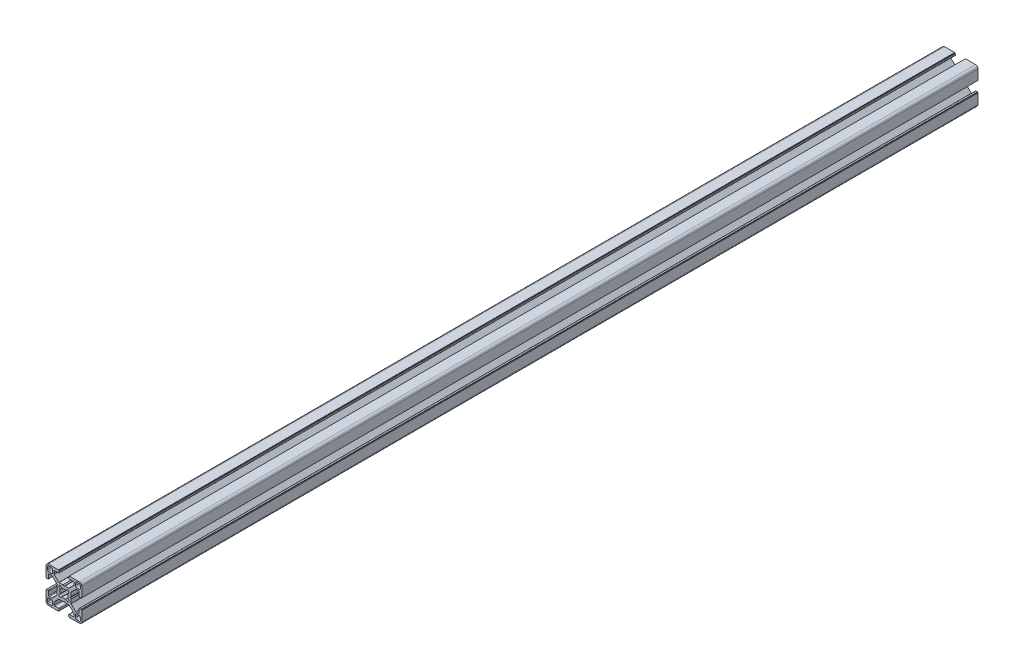
SolidWorks part; units mm, degrees
ref_plane "Front Plane" through (0, 0, 0) normal (0, 0, 1) x (1, 0, 0)
ref_plane "Top Plane" through (0, 0, 0) normal (0, 1, 0) x (1, 0, 0)
ref_plane "Right Plane" through (0, 0, 0) normal (1, 0, 0) x (0, 0, -1)
sketch "Sketch1" plane through (0, 0, 0) normal (0, 0, 1) x (1, 0, 0)
  line L0 (-15, 0) -> (15, 0) construction
  line L1 (0, -15) -> (0, 15) construction
  line L2 (-4.5, 15) -> (4.5, 15) construction
  line L3 (-4, -15) -> (4, -15) construction
  line L4 (-4.5, 15) -> (-4.5, 14.5)
  line L5 (-4.5, 14.5) -> (-4, 14.5)
  line L6 (-4, 14.5) -> (-4, 13.29)
  line L7 (-4.5, 12.79) -> (-7.7675, 12.79)
  line L8 (-8.2675, 12.29) -> (-8.2675, 10.2707)
  line L9 (-8.1211, 9.9171) -> (-4.3504, 6.1464)
  line L10 (-3.9968, 6) -> (0, 6)
  line L11 (0, 0) -> (-15, 15) construction
  line L12 (-4.5, 15) -> (-12.968, 15)
  line L14 (-12.705, 9.5135) -> (-10.5135, 9.5135)
  line L15 (-13.705, 10.5135) -> (-13.705, 12.705)
  line L16 (-12.705, 13.705) -> (-10.5135, 13.705)
  line L17 (-9.5135, 10.5135) -> (-9.5135, 12.705)
  line L18 (-13.705, 9.5135) -> (-9.5135, 13.705) construction
  line L19 (-13.705, 13.705) -> (-9.5135, 9.5135) construction
  line L20 (-3.1568, 4.5038) -> (-1.5303, 3.1477) construction
  line L21 (-4.5038, 3.1568) -> (-3.1477, 1.5303) construction
  line L22 (-6, 3.9968) -> (-6, 0)
  line L23 (-9.9171, 8.1211) -> (-6.1464, 4.3504)
  line L24 (-15, 4.5) -> (-15, 12.968)
  line L25 (-12.29, 8.2675) -> (-10.2707, 8.2675)
  line L26 (-12.79, 4.5) -> (-12.79, 7.7675)
  line L27 (-14.5, 4) -> (-13.29, 4)
  line L28 (-14.5, 4.5) -> (-14.5, 4)
  line L29 (-15, 4.5) -> (-14.5, 4.5)
  circle A0 centre (0, 0) radius 3.5
  arc A1 (-12.968, 15) -> (-15, 12.968) centre (-12.968, 12.968) ccw
  circle A2 centre (0, 0) radius 5.5 construction
  arc A3 (-10.5135, 9.5135) -> (-9.5135, 10.5135) centre (-10.5135, 10.5135) ccw
  arc A4 (-13.705, 12.705) -> (-12.705, 13.705) centre (-12.705, 12.705) cw
  arc A5 (-10.5135, 13.705) -> (-9.5135, 12.705) centre (-10.5135, 12.705) cw
  arc A6 (-12.705, 9.5135) -> (-13.705, 10.5135) centre (-12.705, 10.5135) cw
  arc A7 (-12.79, 4.5) -> (-13.29, 4) centre (-13.29, 4.5) cw
  arc A8 (-12.29, 8.2675) -> (-12.79, 7.7675) centre (-12.29, 7.7675) ccw
  arc A9 (-9.9171, 8.1211) -> (-10.2707, 8.2675) centre (-10.2707, 7.7675) ccw
  arc A10 (-6, 3.9968) -> (-6.1464, 4.3504) centre (-6.5, 3.9968) ccw
  arc A11 (-4.3504, 6.1464) -> (-3.9968, 6) centre (-3.9968, 6.5) ccw
  arc A12 (-4, 13.29) -> (-4.5, 12.79) centre (-4.5, 13.29) cw
  arc A13 (-7.7675, 12.79) -> (-8.2675, 12.29) centre (-7.7675, 12.29) ccw
  arc A14 (-8.2675, 10.2707) -> (-8.1211, 9.9171) centre (-7.7675, 10.2707) ccw
  point P4 (0, 0)
  point P8 (0, 0)
  point P13 (0, 15)
  point P15 (0, -15)
  point P16 (0, 6)
  point P23 (-11.6092, 11.6093)
  point P26 (0, 6)
  point P62 (-12.79, 4)
  point P65 (-12.79, 8.2675)
  point P68 (-10.0636, 8.2675)
  point P71 (-6, 4.2039)
  point P74 (-4.2039, 6)
  point P77 (-4, 12.79)
  point P80 (-8.2675, 12.79)
  point P83 (-8.2675, 10.0636)
  dimension "Center Hole Diameter" = 7
  dimension "D11" = 2.032
  dimension "D9" = 11
  dimension "D13" = 1
  dimension "D14" = 0.5
  dimension "Rail Height" = 30
  dimension "Rail Width" = 30
  dimension "T-Slot Width" = 8
  dimension "T-Slot Depth" = 9
  dimension "D1" = 9
  dimension "D2" = 45
  dimension "D3" = 8
  dimension "D4" = 2.21
  dimension "D5" = 16.535
  dimension "D7" = 2.54
  dimension "D6" = 1.295
  dimension "D8" = 1.246
  dimension "D10" = 10.36
  dimension "D12" = 1.905
sketch "Sketch2" plane through (0, 0, 0) normal (1, 0, 0) x (0, 0, -1)
  line L0 (-76.2, 0) -> (76.2, 0) construction
  line L2 (0, -15) -> (0, 15) construction
  line L3 (0, -15) -> (0, 15) construction
  line L4 (-76.2, -15) -> (-76.2, 15) construction
  line L5 (76.2, -15) -> (76.2, 15) construction
  point P0 (-38.7, 0)
  point P3 (0, 0)
  point P4 (38.7, 0)
  point P12 (-76.2, 0)
  point P14 (76.2, 0)
  dimension "Length" = 152.4
  dimension "D1" = 37.5
sketch "Sketch3" plane through (0, 0, 0) normal (0, 0, 1) x (1, 0, 0)
  line L0 (-4.5038, 3.1568) -> (-3.1477, 1.5303)
  line L1 (0, 3.5) -> (0, 5.5)
  line L2 (-5.5, 0) -> (-3.5, 0)
  line L7 (-6, 3.9968) -> (-6, 0) construction
  line L31 (-9.9171, 8.1211) -> (-6.1464, 4.3504) construction
  line L117 (-12.29, 8.2675) -> (-10.2707, 8.2675) construction
  line L118 (-12.79, 4.5) -> (-12.79, 7.7675) construction
  line L157 (-12.705, 9.5135) -> (-10.5135, 9.5135)
  line L158 (-9.5135, 10.5135) -> (-9.5135, 12.705)
  line L163 (-10.5135, 13.705) -> (-12.705, 13.705)
  line L164 (-13.705, 12.705) -> (-13.705, 10.5135)
  line L165 (-12.705, 9.5135) -> (-10.5135, 9.5135)
  line L166 (-9.5135, 10.5135) -> (-9.5135, 12.705)
  line L167 (-10.5135, 13.705) -> (-12.705, 13.705)
  line L168 (-13.705, 12.705) -> (-13.705, 10.5135)
  line L169 (-14.5, 4) -> (-13.29, 4) construction
  line L170 (-14.5, 4.5) -> (-14.5, 4) construction
  line L171 (-15, 4.5) -> (-14.5, 4.5) construction
  line L172 (-15, 4.5) -> (-15, 12.968) construction
  line L173 (-4.5, 15) -> (-12.968, 15) construction
  line L174 (-4.5, 15) -> (-4.5, 14.5) construction
  line L175 (-4.5, 14.5) -> (-4, 14.5) construction
  line L176 (-4, 14.5) -> (-4, 13.29) construction
  line L177 (-4.5, 12.79) -> (-7.7675, 12.79) construction
  line L178 (-8.2675, 12.29) -> (-8.2675, 10.2707) construction
  line L179 (-8.1211, 9.9171) -> (-4.3504, 6.1464) construction
  line L180 (-3.9968, 6) -> (0, 6) construction
  line L181 (-6, 3.9968) -> (-6, 0.866)
  line L182 (-9.9171, 8.1211) -> (-6.1464, 4.3504)
  line L183 (-12.29, 8.2675) -> (-10.2707, 8.2675)
  line L184 (-12.79, 4.5) -> (-12.79, 7.7675)
  line L185 (-14.5, 4) -> (-13.29, 4)
  line L186 (-14.5, 4.5) -> (-14.5, 4)
  line L187 (-15, 4.5) -> (-14.5, 4.5)
  line L188 (-15, 4.5) -> (-15, 12.968)
  line L189 (-4.5, 15) -> (-12.968, 15)
  line L190 (-4.5, 15) -> (-4.5, 14.5)
  line L191 (-4.5, 14.5) -> (-4, 14.5)
  line L192 (-4, 14.5) -> (-4, 13.29)
  line L193 (-4.5, 12.79) -> (-7.7675, 12.79)
  line L194 (-8.2675, 12.29) -> (-8.2675, 10.2707)
  line L195 (-8.1211, 9.9171) -> (-4.3504, 6.1464)
  line L196 (-3.9968, 6) -> (-0.866, 6)
  line L197 (-0.866, 6) -> (0, 5.5)
  line L198 (0, -15) -> (0, 15) construction
  line L199 (0, 0) -> (-15, 15) construction
  line L200 (0, 0) -> (-15, 15) construction
  line L201 (-3.1568, 4.5038) -> (-1.5303, 3.1477) construction
  line L202 (-3.1568, 4.5038) -> (-1.5303, 3.1477)
  line L203 (-6, 0.866) -> (-5.5, 0)
  line L204 (-15, 0) -> (15, 0) construction
  line L205 (-15, 0) -> (15, 0) construction
  line L206 (0, -15) -> (0, 15) construction
  arc A0 (-3.5, 0) -> (-3.1477, 1.5303) centre (0, 0) cw
  arc A10 (-6, 3.9968) -> (-6.1464, 4.3504) centre (-6.5, 3.9968) ccw construction
  circle A16 centre (0, 0) radius 3.5
  arc A18 (0, 3.5) -> (-1.5303, 3.1477) centre (0, 0) ccw
  arc A20 (-9.9171, 8.1211) -> (-10.2707, 8.2675) centre (-10.2707, 7.7675) ccw construction
  arc A22 (-12.29, 8.2675) -> (-12.79, 7.7675) centre (-12.29, 7.7675) ccw construction
  arc A28 (-13.29, 4) -> (-12.79, 4.5) centre (-13.29, 4.5) ccw construction
  arc A29 (-10.5135, 9.5135) -> (-9.5135, 10.5135) centre (-10.5135, 10.5135) ccw
  arc A30 (-9.5135, 12.705) -> (-10.5135, 13.705) centre (-10.5135, 12.705) ccw
  arc A31 (-12.705, 13.705) -> (-13.705, 12.705) centre (-12.705, 12.705) ccw
  arc A32 (-13.705, 10.5135) -> (-12.705, 9.5135) centre (-12.705, 10.5135) ccw
  arc A33 (-10.5135, 9.5135) -> (-9.5135, 10.5135) centre (-10.5135, 10.5135) ccw
  arc A34 (-9.5135, 12.705) -> (-10.5135, 13.705) centre (-10.5135, 12.705) ccw
  arc A35 (-12.705, 13.705) -> (-13.705, 12.705) centre (-12.705, 12.705) ccw
  arc A36 (-13.705, 10.5135) -> (-12.705, 9.5135) centre (-12.705, 10.5135) ccw
  arc A37 (-12.968, 15) -> (-15, 12.968) centre (-12.968, 12.968) ccw construction
  arc A38 (-4.5, 12.79) -> (-4, 13.29) centre (-4.5, 13.29) ccw construction
  arc A39 (-7.7675, 12.79) -> (-8.2675, 12.29) centre (-7.7675, 12.29) ccw construction
  arc A40 (-8.2675, 10.2707) -> (-8.1211, 9.9171) centre (-7.7675, 10.2707) ccw construction
  arc A41 (-4.3504, 6.1464) -> (-3.9968, 6) centre (-3.9968, 6.5) ccw construction
  arc A42 (-6, 3.9968) -> (-6.1464, 4.3504) centre (-6.5, 3.9968) ccw
  arc A43 (-9.9171, 8.1211) -> (-10.2707, 8.2675) centre (-10.2707, 7.7675) ccw
  arc A44 (-12.29, 8.2675) -> (-12.79, 7.7675) centre (-12.29, 7.7675) ccw
  arc A45 (-13.29, 4) -> (-12.79, 4.5) centre (-13.29, 4.5) ccw
  arc A46 (-12.968, 15) -> (-15, 12.968) centre (-12.968, 12.968) ccw
  arc A47 (-4.5, 12.79) -> (-4, 13.29) centre (-4.5, 13.29) ccw
  arc A48 (-7.7675, 12.79) -> (-8.2675, 12.29) centre (-7.7675, 12.29) ccw
  arc A49 (-8.2675, 10.2707) -> (-8.1211, 9.9171) centre (-7.7675, 10.2707) ccw
  arc A50 (-4.3504, 6.1464) -> (-3.9968, 6) centre (-3.9968, 6.5) ccw
  circle A51 centre (0, 0) radius 5.5 construction
  arc A52 (-3.1568, 4.5038) -> (-4.5038, 3.1568) centre (0, 0) ccw
  dimension "D3" = 60
  dimension "D4" = 60
  dimension "D1" = 0
  dimension "D2" = 0
extrude "Boss-Extrude1" add sketch "Sketch3" along normal mid plane 750
pattern_circular "CirPattern1" count 4 over 360 about axis through (0, 0, 76.2) along (0, 0, -1) of "Boss-Extrude1"
ref_plane "Contact Plane1" through (15, 0, 0) normal (1, 0, 0) x (0, 0, -1)
ref_plane "Contact Plane2" through (0, -15, 0) normal (0, 1, 0) x (1, 0, 0)
ref_plane "Contact Plane3" through (-15, 0, 0) normal (1, 0, 0) x (0, 0, -1)
ref_plane "Contact Plane4" through (0, 15, 0) normal (0, 1, 0) x (1, 0, 0)
equation "\"D1@Sketch2\" = \"Rail Height@Sketch1\" * 1.25"
equation "\"D1@Sketch1\"=\"T-Slot Width@Sketch1\"+1mm"
equation "\"D3@Sketch1\"=\"T-Slot Width@Sketch1\""
equation "\"D1@Boss-Extrude1\"=\"length\""
equation "\"length\" = 750"
